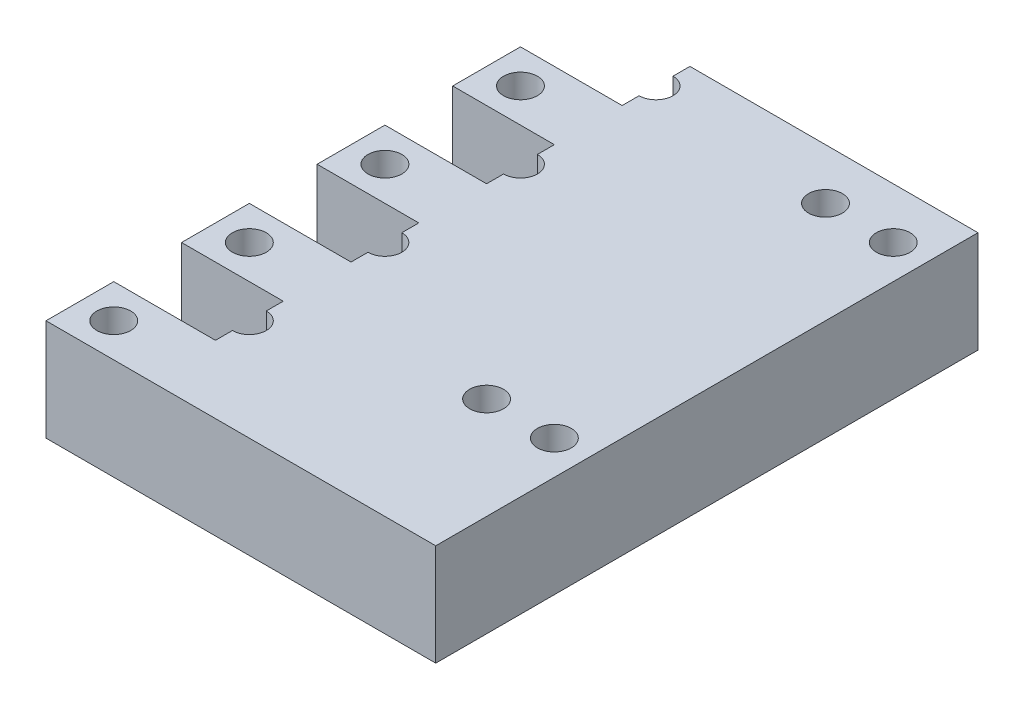
SolidWorks part; units mm, degrees
ref_plane "Front Plane" through (0, 0, 0) normal (0, 0, 1) x (1, 0, 0)
ref_plane "Top Plane" through (0, 0, 0) normal (0, 1, 0) x (1, 0, 0)
ref_plane "Right Plane" through (0, 0, 0) normal (1, 0, 0) x (0, 0, -1)
sketch "Sketch1" plane through (0, 0, 0) normal (0, 1, 0) x (1, 0, 0)
  line L0 (0, 0) -> (0, 4)
  line L1 (0, 4) -> (6, 4)
  line L2 (6, 4) -> (6, 8)
  line L3 (6, 8) -> (0, 8)
  line L4 (0, 8) -> (0, 12)
  line L5 (0, 12) -> (6, 12)
  line L6 (6, 12) -> (6, 16)
  line L7 (6, 16) -> (0, 16)
  line L8 (0, 16) -> (0, 20)
  line L9 (0, 20) -> (6, 20)
  line L10 (6, 20) -> (6, 24)
  line L11 (6, 24) -> (0, 24)
  line L12 (0, 24) -> (0, 28)
  line L13 (0, 28) -> (6, 28)
  line L14 (6, 28) -> (6, 32)
  line L15 (6, 32) -> (23, 32)
  line L16 (23, 32) -> (23, 0)
  line L17 (23, 0) -> (0, 0)
  dimension "D1" = 32
  dimension "D2" = 4
  dimension "D3" = 4
  dimension "D4" = 4
  dimension "D5" = 4
  dimension "D6" = 4
  dimension "D7" = 4
  dimension "D8" = 4
  dimension "D9" = 6
  dimension "D10" = 17
extrude "Boss-Extrude1" add sketch "Sketch1" along normal blind 6
sketch "Sketch2" plane through (0, 6, 0) normal (0, 1, 0) x (1, 0, 0)
  line L0 (0, 28) -> (0, 24) construction
  line L1 (0, 20) -> (0, 16) construction
  line L2 (0, 12) -> (0, 8) construction
  line L3 (0, 4) -> (0, 0) construction
  line L6 (6, 24) -> (6, 20) construction
  line L7 (6, 32) -> (6, 28) construction
  line L8 (6, 16) -> (6, 12) construction
  line L9 (6, 8) -> (6, 4) construction
  line L10 (23, 0) -> (23, 32) construction
  line L11 (0, 0) -> (23, 0) construction
  line L12 (23, 32) -> (6, 32) construction
  circle A0 centre (2, 26) radius 1
  circle A1 centre (2, 18) radius 1
  circle A2 centre (2, 10) radius 1
  circle A3 centre (2, 2) radius 1
  circle A4 centre (6, 22) radius 1
  circle A5 centre (6, 30) radius 1
  circle A6 centre (6, 14) radius 1
  circle A7 centre (6, 6) radius 1
  circle A8 centre (21, 29) radius 1
  circle A9 centre (21, 9) radius 1
  circle A10 centre (17, 29) radius 1
  circle A11 centre (17, 9) radius 1
  point P8 (0, 26)
  point P13 (0, 18)
  point P16 (0, 10)
  point P19 (0, 2)
  dimension "D1" = 2
  dimension "D3" = 2
  dimension "D2" = 2
  dimension "D4" = 2
  dimension "D5" = 9
  dimension "D6" = 3
  dimension "D7" = 4
extrude "Cut-Extrude1" cut sketch "Sketch2" against normal through all
